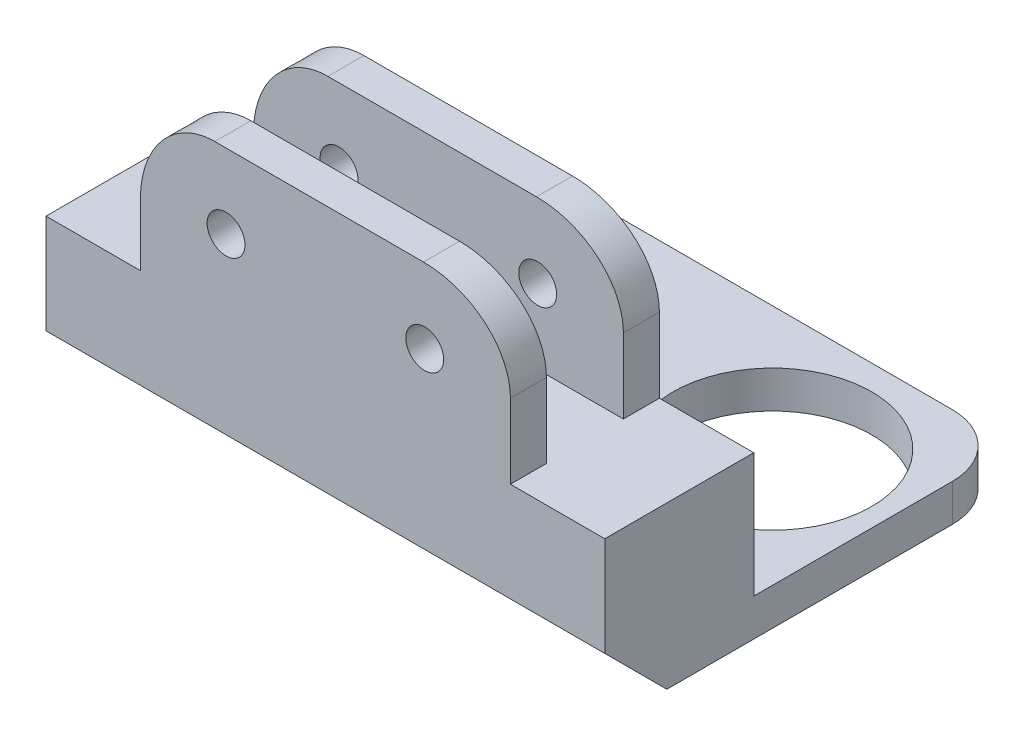
SolidWorks part; units mm, degrees
note: The reader was unsure of these and kept them because the rebuilt part matched: shared geometry of "Sketch3<3>".
other "Markup1"
sketch "Sketch5" plane through (-22.5, 15, -10) normal (-0.7043, 0.3825, -0.598) x (0.4709, 0.8821, 0.0097)
ref_plane "Front Plane" through (0, 0, 0) normal (0, 0, 1) x (1, 0, 0)
ref_plane "Top Plane" through (0, 0, 0) normal (0, 1, 0) x (1, 0, 0)
ref_plane "Right Plane" through (0, 0, 0) normal (1, 0, 0) x (0, 0, -1)
sketch "Sketch1" plane through (0, 0, 0) normal (0, 1, 0) x (1, 0, 0)
  line L1 (-22.5, -10) -> (22.5, -10)
  line L2 (-22.5, -10) -> (-22.5, 10)
  line L3 (-22.5, 10) -> (22.5, 10)
  line L4 (22.5, -10) -> (22.5, 10)
  line L5 (-22.5, -10) -> (22.5, 10) construction
  line L6 (-22.5, 10) -> (22.5, -10) construction
  line L7 (-22.5, -10) -> (22.5, -10)
  line L8 (-22.5, -10) -> (-22.5, -23)
  line L9 (-22.5, -23) -> (22.5, -23)
  line L10 (22.5, -10) -> (22.5, -23)
  line L11 (-22.5, -10) -> (22.5, -10)
  line L12 (-22.5, -10) -> (-22.5, -11)
  line L13 (-22.5, -11) -> (22.5, -11)
  line L14 (22.5, -10) -> (22.5, -11)
  circle A0 centre (-13, 0) radius 8
  circle A1 centre (13, 0) radius 8
  point P0 (0, 0)
  dimension "D3" = 16
  dimension "D6" = 16
  dimension "D1" = 45
  dimension "D2" = 20
  dimension "D4" = 13
  dimension "D5" = 13
  dimension "D7" = 13
  dimension "D8" = 1
extrude "Boss-Extrude1" add sketch "Sketch1" along normal blind 3 contours L1 L4 L3 L2 A1 A0 | L10 L1 L8 L9 | L8 L13 L10 L1
sketch "Sketch3" plane through (0, 3, 0) normal (0, 1, 0) x (1, 0, 0)
  line L0 (22.5, -23) -> (22.5, 10) construction
  line L1 (-22.5, -23) -> (22.5, -23)
  line L2 (-22.5, -23) -> (-22.5, -11)
  line L3 (-22.5, -11) -> (22.5, -11)
  line L4 (22.5, -23) -> (22.5, -11)
  line L6 (-22.5, -11) -> (22.5, -11)
  line L7 (-22.5, -11) -> (-22.5, -13.9)
  line L8 (-22.5, -13.9) -> (22.5, -13.9)
  line L9 (22.5, -11) -> (22.5, -13.9)
  line L10 (-22.5, -23) -> (22.5, -23)
  line L11 (-22.5, -23) -> (-22.5, -20.1)
  line L12 (-22.5, -20.1) -> (22.5, -20.1)
  line L13 (22.5, -23) -> (22.5, -20.1)
  line M12 (-22.5, 10) -> (-22.5, -23)
  line M13 (-22.5, -23) -> (22.5, -23)
  line M14 (22.5, -23) -> (22.5, 10)
  dimension "D1" = 2.9
  dimension "D2" = 12
  dimension "D3" = 2.9
extrude "Boss-Extrude2" add sketch "Sketch3" along normal blind 10 contours L12 M12 M13 M14 | L2 L12 L4 L8 | L8 L4 L3 M12
extrude "Boss-Extrude3" add sketch "Sketch3<3>" along normal blind 22 contours L8 L4 L3 M12 | L12 M12 M13 M14
sketch "Sketch3<3>" plane through (0, 3, 0) normal (0, 1, 0) x (1, 0, 0) same geometry as "Sketch3"
sketch "Sketch6" plane through (0, 0, 11) normal (0, 0, -1) x (-1, 0, 0)
  line L0 (22.5, 25) -> (-22.5, 25) construction
  line L1 (-14.9, 25) -> (14.9, 25)
  line L2 (-14.9, 25) -> (-14.9, 13)
  line L3 (-14.9, 13) -> (14.9, 13)
  line L4 (14.9, 25) -> (14.9, 13)
  line L5 (-22.5, 25) -> (-22.5, 3) construction
  line L6 (-14.9, 25) -> (-22.5, 25)
  line L7 (-14.9, 25) -> (-14.9, 13)
  line L8 (-14.9, 25) -> (-14.9, 13)
  line L9 (14.9, 25) -> (22.6772, 25)
  line L10 (14.9, 25) -> (14.9, 13)
  line L11 (14.9, 13) -> (22.6772, 13)
  line L12 (22.6772, 25) -> (22.6772, 13)
  line L13 (-14.9, 13) -> (-22.5, 13)
  line L14 (-22.5, 25) -> (-22.5, 13)
  circle A0 centre (-8, 19) radius 1.525
  circle A1 centre (8, 19) radius 1.525
  point P6 (0, 13)
  point P23 (-14.9, 19)
  line M6 (22.5, 3) -> (22.5, 25)
  line M7 (22.5, 25) -> (-22.5, 25)
  line M8 (-22.5, 25) -> (-22.5, 3)
  dimension "D4" = 3.05
  dimension "D6" = 3.05
  dimension "D1" = 12
  dimension "D2" = 29.8
  dimension "D3" = 6.9
  dimension "D5" = 6.9
extrude "Cut-Extrude2" cut sketch "Sketch6" against normal blind 16.5 contours A0 | A1 | L13 L2 M7 M8 | L4 L11 M6 M7
chamfer "Chamfer1" distance 5 angle 45 1 edges at (0, 0, 23)
fillet "Fillet2" radius 5 2 edges at (-22.5, 1.5, -10) (22.5, 1.5, -10)
fillet "Fillet3" radius 6 4 edges at (14.9, 25, 12.45) (14.9, 25, 21.55) (-14.9, 25, 21.55) (-14.9, 25, 12.45)
